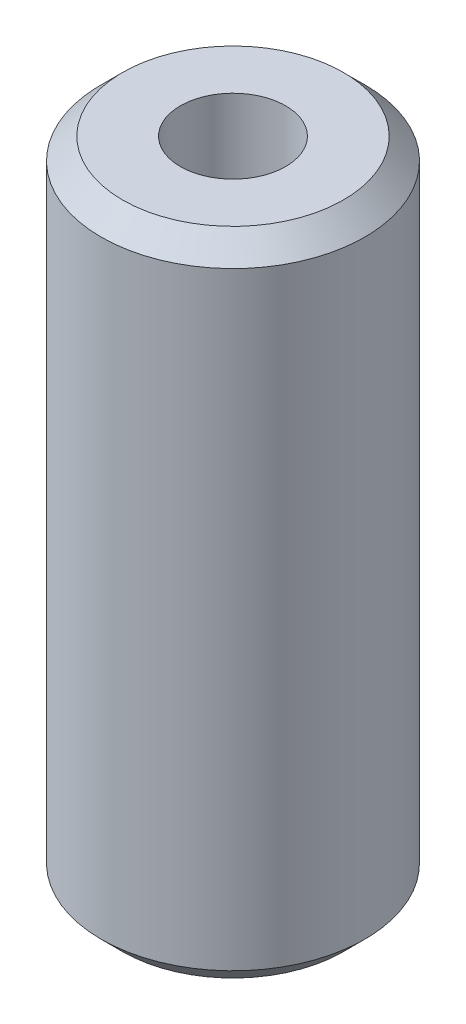
SolidWorks part; units mm, degrees
ref_plane "Front Plane" through (0, 0, 0) normal (0, 0, 1) x (1, 0, 0)
ref_plane "Top Plane" through (0, 0, 0) normal (0, 1, 0) x (1, 0, 0)
ref_plane "Right Plane" through (0, 0, 0) normal (1, 0, 0) x (0, 0, -1)
sketch "Sketch1" plane through (0, 0, 0) normal (0, 1, 0) x (1, 0, 0)
  circle A0 centre (0, 0) radius 27.5
  dimension "SHAFT_OD" = 55
extrude "Boss-Extrude1" add sketch "Sketch1" along normal blind 135.7326
sketch "Sketch2" plane through (0, 0, 0) normal (0, 1, 0) x (1, 0, 0)
  circle A0 centre (0, 0) radius 10.9808
  dimension "BORE_D" = 21.9616
extrude "Cut-Extrude1" cut sketch "Sketch2" along normal through all
chamfer "Chamfer1" distance 4.4673 angle 45 2 edges at (0, 135.7326, 27.5) (0, 0, 27.5)
